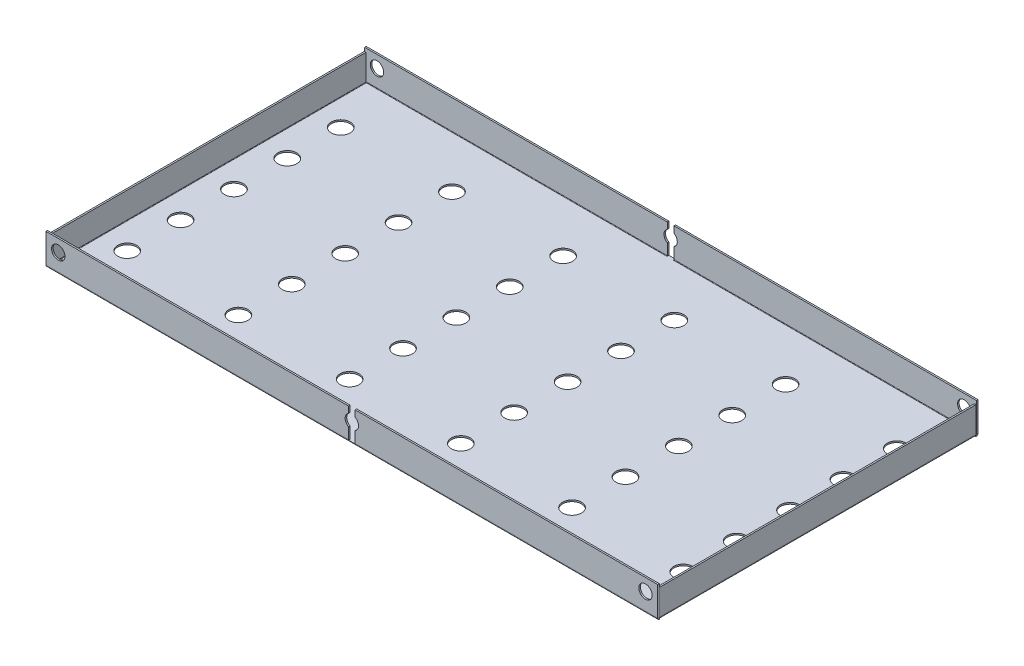
SolidWorks part; units mm, degrees
note: The reader was unsure of these and kept them because the rebuilt part matched: flange length of "边线-法兰1", "边线-法兰2".
material "1023 碳钢板 (SS)"
ref_plane "前视基准面" through (0, 0, 0) normal (0, 0, 1) x (1, 0, 0)
ref_plane "上视基准面" through (0, 0, 0) normal (0, 1, 0) x (1, 0, 0)
ref_plane "右视基准面" through (0, 0, 0) normal (1, 0, 0) x (0, 0, -1)
sketch "草图1" plane through (0, 0, 0) normal (0, 1, 0) x (1, 0, 0)
  line L0 (-100, 72) -> (-100, -72) construction
  line L1 (-137.5, 72) -> (137.5, 72)
  line L2 (-137.5, 72) -> (-137.5, -72)
  line L3 (-137.5, -72) -> (137.5, -72)
  line L5 (-137.5, -72) -> (137.5, 72) construction
  line L6 (-137.5, 72) -> (137.5, -72) construction
  line L7 (-50, 72) -> (-50, -72) construction
  line L8 (0, 0) -> (0, -72) construction
  line L10 (137.5, 72) -> (137.5, -72)
  circle A0 centre (-125, -48) radius 4.25
  circle A1 centre (-125, -24) radius 4.25
  circle A2 centre (-125, 0) radius 4.25
  circle A3 centre (-125, 24) radius 4.25
  circle A4 centre (-125, 48) radius 4.25
  circle A5 centre (-75, -48) radius 4.25
  circle A6 centre (-75, -24) radius 4.25
  circle A7 centre (-75, 0) radius 4.25
  circle A8 centre (-75, 24) radius 4.25
  circle A9 centre (-75, 48) radius 4.25
  circle A40 centre (-25, -48) radius 4.25
  circle A41 centre (-25, -24) radius 4.25
  circle A42 centre (-25, 0) radius 4.25
  circle A43 centre (-25, 24) radius 4.25
  circle A44 centre (-25, 48) radius 4.25
  circle A45 centre (25, -48) radius 4.25
  circle A46 centre (25, -24) radius 4.25
  circle A47 centre (25, 0) radius 4.25
  circle A48 centre (25, 24) radius 4.25
  circle A49 centre (25, 48) radius 4.25
  circle A50 centre (75, 48) radius 4.25
  circle A51 centre (75, 24) radius 4.25
  circle A52 centre (75, 0) radius 4.25
  circle A53 centre (75, -24) radius 4.25
  circle A54 centre (75, -48) radius 4.25
  circle A55 centre (125, -48) radius 4.25
  circle A56 centre (125, -24) radius 4.25
  circle A57 centre (125, 0) radius 4.25
  circle A58 centre (125, 24) radius 4.25
  circle A59 centre (125, 48) radius 4.25
  point P0 (0, 0)
  point P70 (0, 0)
  point P71 (0, 0)
  dimension "D5" = 8.5
  dimension "D6" = 24
  dimension "D18" = 275
  dimension "D2" = 144
  dimension "D3" = 24
  dimension "D4" = 12.5
  dimension "D7" = 24
  dimension "D8" = 24
  dimension "D9" = 24
  dimension "D10" = 24
  dimension "D14" = 25
  dimension "D15" = 50
  dimension "D16" = 50
base flange "基体-法兰1" sketch "草图1" thickness 0.7 reverse thickness direction no parameters "D1"=0.2
edge flange "边线-法兰1" sketch "草图12" flange profiles "草图12", "草图13" flange angle 90 flange length 14 flange position material inside bend radius 0.2 thickness 0.7 relief rectangular parameters "D6"=10, "D8"=1
sketch "草图12" plane through (0, 0, 72) normal (0, 0, 1) x (1, 0, 0)
  line L2 (-137.5, 0) -> (-137.5, 13.3)
  line L3 (-137.5, 13.3) -> (137.5, 13.3)
  line L4 (137.5, 13.3) -> (137.5, 0)
  line L11 (-137.5, 0) -> (137.5, 0) construction
  line L12 (-137.5, 0) -> (137.5, 0)
sketch "草图13" plane through (0, 0, -72) normal (0, 0, -1) x (-1, 0, 0)
  line L2 (-137.5, 0) -> (-137.5, 13.3)
  line L3 (-137.5, 13.3) -> (137.5, 13.3)
  line L4 (137.5, 13.3) -> (137.5, 0)
  line L7 (-137.5, 0) -> (137.5, 0) construction
  line L8 (-137.5, 0) -> (137.5, 0)
bend "边线折弯1" bend radius 0.2 bend angle 90 parameters "D5"=1
bend "边线折弯2" bend radius 0.2 bend angle 90 parameters "D5"=2
sketch "草图14" plane through (0, 0, 71.3) normal (0, 0, -1) x (-1, 0, 0)
  line L0 (0, 13.3) -> (0, 0) construction
  line L1 (137.5, 13.3) -> (-137.5, 13.3) construction
  line L2 (-137.5, 13.3) -> (-137.5, 0.2) construction
  circle A0 centre (-132, 7.8) radius 3
  circle A1 centre (0, 7.8) radius 3
  circle A2 centre (132, 7.8) radius 3
  dimension "D1" = 6
  dimension "D2" = 5.5
  dimension "D3" = 5.5
  dimension "D4" = 5.5
  dimension "D5" = 6
extrude "切除-拉伸1" cut sketch "草图14" against normal blind 10
sketch "草图15" plane through (0, 0, -72) normal (0, 0, -1) x (-1, 0, 0)
  line L0 (0, 13.3) -> (0, 0) construction
  line L1 (137.5, 13.3) -> (-137.5, 13.3) construction
  line L2 (-137.5, 13.3) -> (-137.5, 0.2) construction
  circle A0 centre (-132, 7.8) radius 3
  circle A1 centre (0, 7.8) radius 3
  circle A2 centre (132, 7.8) radius 3
  dimension "D1" = 6
  dimension "D2" = 5.5
  dimension "D3" = 6
  dimension "D4" = 5.5
  dimension "D5" = 5.5
extrude "切除-拉伸2" cut sketch "草图15" against normal blind 10
sketch "草图16" plane through (0, 0, -72) normal (0, 0, -1) x (-1, 0, 0)
  line L0 (0, 0) -> (0, 13.3) construction
  line L1 (137.5, 13.3) -> (-137.5, 13.3) construction
  line L2 (1.5, 0) -> (1.5, 13.3)
  line L3 (-1.5, 0) -> (-1.5, 13.3)
  line L4 (-1.5, 13.3) -> (1.5, 13.3)
  line L5 (-1.5, 0) -> (1.5, 0)
  dimension "D1" = 1.5
  dimension "D2" = 1.5
extrude "切除-拉伸3" cut sketch "草图16" against normal blind 10
sketch "草图17" plane through (0, 0, 72) normal (0, 0, 1) x (1, 0, 0)
  line L0 (0, 0) -> (0, 13.3) construction
  line L1 (137.5, 13.3) -> (-137.5, 13.3) construction
  line L2 (1.5, 0) -> (1.5, 13.3)
  line L3 (-1.5, 0) -> (-1.5, 13.3)
  line L4 (-1.5, 13.3) -> (1.5, 13.3)
  line L5 (-1.5, 0) -> (1.5, 0)
  dimension "D1" = 1.5
  dimension "D2" = 1.5
extrude "切除-拉伸4" cut sketch "草图17" against normal blind 10
edge flange "边线-法兰2" sketch "草图22" flange profiles "草图22", "草图23" flange angle 90 flange length 12.5 flange position material inside bend radius 0.2 thickness 0.7 relief none parameters "D6"=10, "D8"=1
sketch "草图22" plane through (-137.5, 0, 0) normal (-1, 0, 0) x (0, 0, 1)
  line L2 (-71.1, 0) -> (-71.1, 11.8)
  line L3 (-71.1, 11.8) -> (71.1, 11.8)
  line L4 (71.1, 11.8) -> (71.1, 0)
  line L11 (-71.1, 0) -> (71.1, 0) construction
  line L12 (-71.1, 0) -> (71.1, 0)
sketch "草图23" plane through (137.5, 0, 0) normal (1, 0, 0) x (0, 0, -1)
  line L2 (71.1, 0) -> (71.1, 11.8)
  line L3 (71.1, 11.8) -> (-71.1, 11.8)
  line L4 (-71.1, 11.8) -> (-71.1, 0)
  line L9 (-71.1, 0) -> (71.1, 0) construction
  line L10 (-71.1, 0) -> (71.1, 0)
bend "边线折弯3" bend radius 0.2 bend angle 90 parameters "D5"=3
bend "边线折弯4" bend radius 0.2 bend angle 90 parameters "D5"=4
sketch "折弯-线1" [suppressed] plane through (0, 0, 0) normal (0, 1, 0) x (1, 0, 0)
sketch "边界框1" [suppressed] plane through (0, 0, 0) normal (0, 1, 0) x (1, 0, 0)
sheet metal parameters "钣金6" thickness 0.7 parameters "D1"=0.2
flat pattern "平板型式6" [suppressed]
sketch "折弯-线2" plane through (0, 0, 0) normal (0, 1, 0) x (1, 0, 0)
sketch3d "边界框2" [suppressed]
  line L0 (200, -72, 0) -> (-200, -72, 0) construction
  line L1 (200, 72, 0) -> (-200, 72, 0) construction
  line L2 (200, -72, 0) -> (200, 72, 0) construction
  line L3 (-200, -72, 0) -> (-200, 72, 0) construction
sheet metal parameters "钣金7" thickness 0.7 parameters "D1"=0.2
flat pattern "平板型式6" [suppressed]
sketch "折弯-线2" plane through (0, 0, 0) normal (0, 1, 0) x (1, 0, 0)
sketch3d "边界框2" [suppressed]
  line L0 (200, -72, 0) -> (-200, -72, 0) construction
  line L1 (200, 72, 0) -> (-200, 72, 0) construction
  line L2 (200, -72, 0) -> (200, 72, 0) construction
  line L3 (-200, -72, 0) -> (-200, 72, 0) construction
bend of the flat pattern "展平-<边线折弯1>1"
bend of the flat pattern "展平-<边线折弯2>1"
sheet metal parameters "钣金8" thickness 0.7 parameters "D1"=0.2
flat pattern "平板型式6" [suppressed]
sketch "折弯-线2" plane through (0, 0, 0) normal (0, 1, 0) x (1, 0, 0)
sketch3d "边界框2" [suppressed]
  line L0 (200, -72, 0) -> (-200, -72, 0) construction
  line L1 (200, 72, 0) -> (-200, 72, 0) construction
  line L2 (200, -72, 0) -> (200, 72, 0) construction
  line L3 (-200, -72, 0) -> (-200, 72, 0) construction
bend of the flat pattern "展平-<边线折弯1>1"
bend of the flat pattern "展平-<边线折弯2>1"
sheet metal parameters "钣金9" thickness 0.7 parameters "D1"=0.2
flat pattern "平板型式6" [suppressed]
sketch "折弯-线2" plane through (0, 0, 0) normal (0, 1, 0) x (1, 0, 0)
sketch3d "边界框2" [suppressed]
  line L0 (200, -72, 0) -> (-200, -72, 0) construction
  line L1 (200, 72, 0) -> (-200, 72, 0) construction
  line L2 (200, -72, 0) -> (200, 72, 0) construction
  line L3 (-200, -72, 0) -> (-200, 72, 0) construction
bend of the flat pattern "展平-<边线折弯1>1"
bend of the flat pattern "展平-<边线折弯2>1"
sheet metal parameters "钣金10" thickness 0.7 parameters "D1"=0.2
flat pattern "平板型式6" [suppressed]
sketch "折弯-线2" plane through (0, 0, 0) normal (0, 1, 0) x (1, 0, 0)
sketch3d "边界框2" [suppressed]
  line L0 (200, -72, 0) -> (-200, -72, 0) construction
  line L1 (200, 72, 0) -> (-200, 72, 0) construction
  line L2 (200, -72, 0) -> (200, 72, 0) construction
  line L3 (-200, -72, 0) -> (-200, 72, 0) construction
bend of the flat pattern "展平-<边线折弯1>1"
bend of the flat pattern "展平-<边线折弯2>1"
sheet metal parameters "钣金11" thickness 0.7 parameters "D1"=0.2
flat pattern "平板型式6" [suppressed]
sketch "折弯-线2" plane through (0, 0, 0) normal (0, 1, 0) x (1, 0, 0)
sketch3d "边界框2" [suppressed]
  line L0 (200, -72, 0) -> (-200, -72, 0) construction
  line L1 (200, 72, 0) -> (-200, 72, 0) construction
  line L2 (200, -72, 0) -> (200, 72, 0) construction
  line L3 (-200, -72, 0) -> (-200, 72, 0) construction
bend of the flat pattern "展平-<边线折弯1>1"
bend of the flat pattern "展平-<边线折弯2>1"
sheet metal parameters "钣金12" thickness 0.7 parameters "D1"=0.2
flat pattern "平板型式6" [suppressed]
sketch "折弯-线2" plane through (0, 0, 0) normal (0, 1, 0) x (1, 0, 0)
sketch3d "边界框2" [suppressed]
  line L0 (200, -72, 0) -> (-200, -72, 0) construction
  line L1 (200, 72, 0) -> (-200, 72, 0) construction
  line L2 (200, -72, 0) -> (200, 72, 0) construction
  line L3 (-200, -72, 0) -> (-200, 72, 0) construction
bend of the flat pattern "展平-<边线折弯1>1"
bend of the flat pattern "展平-<边线折弯2>1"
bend of the flat pattern "展平-<边线折弯3>1"
bend of the flat pattern "展平-<边线折弯4>1"
